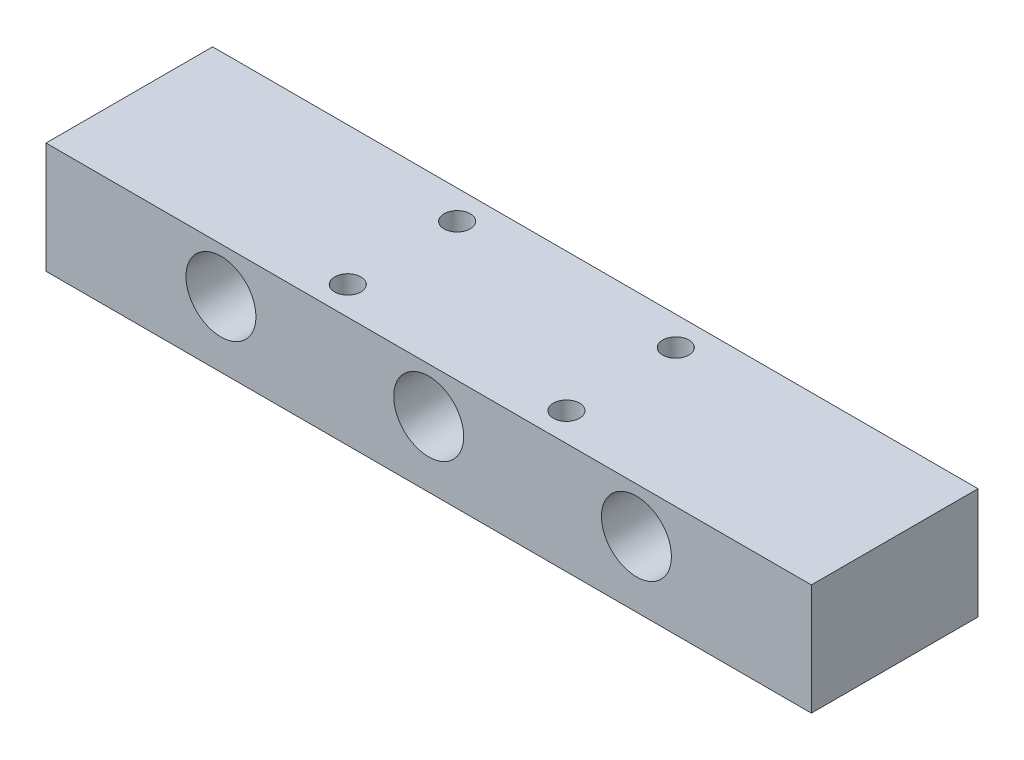
SolidWorks part; units mm, degrees
ref_plane "Front Plane" through (0, 0, 0) normal (0, 0, 1) x (1, 0, 0)
ref_plane "Top Plane" through (0, 0, 0) normal (0, 1, 0) x (1, 0, 0)
ref_plane "Right Plane" through (0, 0, 0) normal (1, 0, 0) x (0, 0, -1)
sketch "Sketch1" plane through (0, 0, 0) normal (0, 1, 0) x (1, 0, 0)
  line L1 (0, 0) -> (350, 0)
  line L2 (0, 0) -> (0, 76.2)
  line L3 (0, 76.2) -> (350, 76.2)
  line L4 (350, 0) -> (350, 76.2)
  dimension "D1" = 76.2
  dimension "D2" = 350
extrude "Boss-Extrude1" add sketch "Sketch1" along normal blind 50.8
sketch "Sketch3" plane through (0, 50.8, 0) normal (0, 1, 0) x (1, 0, 0)
  line L1 (0, 0) -> (175, 0)
  line L2 (0, 0) -> (0, 38)
  line L3 (0, 38) -> (175, 38)
  line L4 (175, 0) -> (175, 38)
  line L5 (125, 63) -> (225, 63)
  line L6 (125, 63) -> (125, 13)
  line L7 (125, 13) -> (225, 13)
  line L8 (225, 63) -> (225, 13)
  line L9 (125, 63) -> (225, 13) construction
  line L10 (125, 13) -> (225, 63) construction
  circle A0 centre (125, 63) radius 6
  circle A1 centre (125, 13) radius 6
  circle A2 centre (225, 63) radius 6
  circle A3 centre (225, 13) radius 6
  dimension "D1" = 175
  dimension "D2" = 38
  dimension "D3" = 100
  dimension "D4" = 50
extrude "Cut-Extrude2" cut sketch "Sketch3" against normal blind 50.8 contours A2 | A1 | A3 | A0
sketch "Sketch5" plane through (0, 0, 0) normal (0, 0, 1) x (1, 0, 0)
  line L0 (175, 30) -> (270, 30)
  line L1 (0, 0) -> (175, 0)
  line L2 (0, 0) -> (0, 30)
  line L4 (175, 0) -> (175, 30)
  line L5 (175, 30) -> (80, 30)
  circle A0 centre (175, 30) radius 16
  circle A1 centre (80, 30) radius 16
  circle A2 centre (270, 30) radius 16
  dimension "D3" = 95
  dimension "D1" = 30
  dimension "D2" = 175
  dimension "D4" = 95
extrude "Cut-Extrude3" cut sketch "Sketch5" against normal through all contours A1 | L0 A0 L5 | L4 A0 L0 | L5 A0 L4 | A2 region at (175, 36.7906, 0) region at (181.7906, 23.2094, 0) region at (168.2094, 23.2094, 0) region at (270, 45.5475, 0) region at (64.4525, 30, 0)
